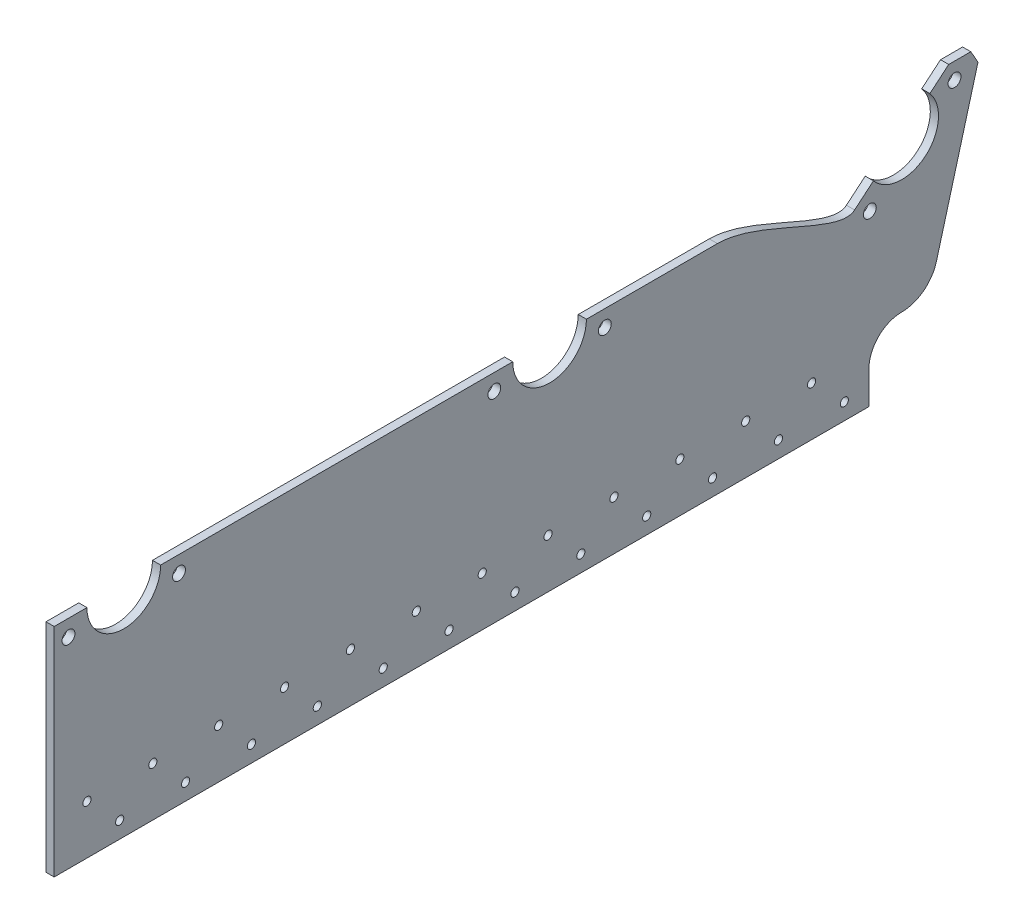
SolidWorks part; units mm, degrees
material "6061 Alloy"
ref_plane "Front Plane" through (0, 0, 0) normal (0, 0, 1) x (1, 0, 0)
ref_plane "Top Plane" through (0, 0, 0) normal (0, 1, 0) x (1, 0, 0)
ref_plane "Right Plane" through (0, 0, 0) normal (1, 0, 0) x (0, 0, -1)
sketch "Sketch1" plane through (0, 0, 0) normal (1, 0, 0) x (0, 0, -1)
  line L0 (-12.7, -12.7) -> (-328.6125, -12.7)
  line L1 (-328.6125, -12.7) -> (-328.6125, 71.4375)
  line L2 (-328.6125, 71.4375) -> (-315.9125, 71.4375)
  line L3 (-287.3375, 71.4375) -> (-150.8125, 71.4375)
  line L5 (10.9449, 80.6213) -> (18.2432, 86.7453)
  line L7 (-328.6125, 12.7) -> (13.4735, 12.7) construction
  line L8 (-12.7, -12.7) -> (-12.7, 0)
  line L9 (0, 12.4079) -> (0, 12.7) construction
  line L10 (13.4735, 22.9788) -> (30.9432, 86.7453)
  line L12 (-10.9449, 62.2537) -> (10.9449, 80.6213) construction
  line L13 (18.2432, 86.7453) -> (30.9432, 86.7453)
  line L14 (-122.2375, 71.4375) -> (-71.4375, 71.4375)
  line L15 (-10.9449, 62.2537) -> (-18.2432, 56.1297)
  line L16 (-328.6125, 15.875) -> (13.4735, 15.875) construction
  line L18 (0, 71.4375) -> (-136.525, 71.4375) construction
  arc A3 (0, 12.7) -> (13.4735, 22.9788) centre (0, 26.67) ccw
  arc A4 (0, 12.7) -> (-12.7, 0) centre (0, 0) ccw
  circle A5 centre (0, 0) radius 12.4079 construction
  arc A6 (-315.9125, 71.4375) -> (-287.3375, 71.4375) centre (-301.625, 71.4375) ccw
  arc A7 (-150.8125, 71.4375) -> (-122.2375, 71.4375) centre (-136.525, 71.4375) ccw
  arc A8 (-10.9449, 62.2537) -> (10.9449, 80.6213) centre (0, 71.4375) ccw
  spline S0 degree 3 poles (-18.2432, 56.1297) (-24.729, 50.6874) (-54.5042, 71.4375) (-71.4375, 71.4375) knots 0 0 0 0 1 1 1 1
  point P4 (-170.6562, -12.7)
  dimension "D1" = 25.4
  dimension "D3" = 12.7
  dimension "D5" = 28.575
  dimension "D6" = 41.275
  dimension "D7" = 13.97
  dimension "D8" = 12.7
  dimension "D10" = 24.8158
  dimension "D13" = 9.5273
  dimension "D14" = 140
  dimension "D15" = 50.8
  dimension "D16" = 50.8
  dimension "D17" = 25.4
  dimension "D2" = 0
  dimension "D4" = 12.7
  dimension "D9" = 12.7
  dimension "D11" = 301.625
  dimension "D12" = 301.625
  dimension "D18" = 3.175
extrude "Boss-Extrude1" add sketch "Sketch1" along normal blind 3.175
hole_wizard "#10 Clearance Hole1" positions "Sketch2" profile "Sketch3" hole size "#10" standard "ANSI Inch" end condition through all
sketch "Sketch2" plane through (3.175, 0, 0) normal (1, 0, 0) x (0, 0, -1)
  line L0 (-323.0562, 65.0875) -> (-280.1937, 65.0875) construction
  line L2 (-157.9562, 65.0875) -> (-115.0938, 65.0875) construction
  line L4 (-12.3356, 52.7974) -> (20.499, 80.3489) construction
  line L6 (-315.9125, 71.4375) -> (-328.6125, 71.4375) construction
  line L7 (-301.625, 65.0875) -> (-301.625, 71.4375) construction
  line L9 (-136.525, 71.4375) -> (-136.525, 65.0875) construction
  line L11 (0, 71.4375) -> (4.0817, 66.5731) construction
  line L14 (18.2432, 86.7453) -> (10.9449, 80.6213) construction
  line L15 (18.2432, 86.7453) -> (10.9449, 80.6213) construction
  point P0 (-323.0562, 65.0875)
  point P2 (-280.1937, 65.0875)
  point P4 (-157.9562, 65.0875)
  point P6 (-115.0938, 65.0875)
  point P8 (-12.3356, 52.7974)
  point P10 (20.499, 80.3489)
  dimension "D1" = 42.8625
  dimension "D2" = 6.35
  dimension "D3" = 6.35
sketch "Sketch3" plane through (3.175, 65.0875, 323.0562) normal (0, 1, 0) x (0, 0, -1)
  line L0 (0, 0) -> (0, 3.175)
  line L1 (0, 3.175) -> (2.4892, 3.175)
  line L2 (2.4892, 3.175) -> (2.4892, 0)
  line L5 (2.4892, 0) -> (0, 0)
  line L11 (0, -6.35) -> (0, 107.95) construction
  dimension "Thru Hole Dia." = 4.9784
  dimension "Thru Hole Depth" = 3.175
chamfer "Chamfer1" distance 5.08 angle 45 1 edges at (1.5875, 86.7453, -30.9432) first distance on face at (1.5875, 54.862, -22.2083)
sketch "Sketch4" plane through (3.175, 0, 0) normal (1, 0, 0) x (0, 0, -1)
  circle A0 centre (-315.9125, 6.35) radius 1.5875 construction
  circle A1 centre (-303.2125, -6.35) radius 1.5875 construction
  circle A2 centre (-290.3682, 6.35) radius 1.5875 construction
  circle A3 centre (-277.6682, -6.35) radius 1.5875 construction
  circle A4 centre (-264.8239, 6.35) radius 1.5875 construction
  circle A5 centre (-252.1239, -6.35) radius 1.5875 construction
  circle A6 centre (-239.2795, 6.35) radius 1.5875 construction
  circle A7 centre (-226.5795, -6.35) radius 1.5875 construction
  circle A8 centre (-213.7352, 6.35) radius 1.5875 construction
  circle A9 centre (-201.0352, -6.35) radius 1.5875 construction
  circle A10 centre (-188.1909, 6.35) radius 1.5875 construction
  circle A11 centre (-175.4909, -6.35) radius 1.5875 construction
  circle A12 centre (-162.6466, 6.35) radius 1.5875 construction
  circle A13 centre (-149.9466, -6.35) radius 1.5875 construction
  circle A14 centre (-137.1023, 6.35) radius 1.5875 construction
  circle A15 centre (-124.4023, -6.35) radius 1.5875 construction
  circle A16 centre (-111.558, 6.35) radius 1.5875 construction
  circle A17 centre (-98.858, -6.35) radius 1.5875 construction
  circle A18 centre (-86.0136, 6.35) radius 1.5875 construction
  circle A19 centre (-73.3136, -6.35) radius 1.5875 construction
  circle A20 centre (-60.4693, 6.35) radius 1.5875 construction
  circle A21 centre (-47.7693, -6.35) radius 1.5875 construction
  circle A22 centre (-34.925, 6.35) radius 1.5875 construction
  circle A23 centre (-22.225, -6.35) radius 1.5875 construction
  circle A24 centre (-315.9125, 6.35) radius 1.5875
  circle A25 centre (-303.2125, -6.35) radius 1.5875
  circle A26 centre (-290.3682, 6.35) radius 1.5875
  circle A27 centre (-277.6682, -6.35) radius 1.5875
  circle A28 centre (-264.8239, 6.35) radius 1.5875
  circle A29 centre (-252.1239, -6.35) radius 1.5875
  circle A30 centre (-239.2795, 6.35) radius 1.5875
  circle A31 centre (-226.5795, -6.35) radius 1.5875
  circle A32 centre (-213.7352, 6.35) radius 1.5875
  circle A33 centre (-201.0352, -6.35) radius 1.5875
  circle A34 centre (-188.1909, 6.35) radius 1.5875
  circle A35 centre (-175.4909, -6.35) radius 1.5875
  circle A36 centre (-162.6466, 6.35) radius 1.5875
  circle A37 centre (-149.9466, -6.35) radius 1.5875
  circle A38 centre (-137.1023, 6.35) radius 1.5875
  circle A39 centre (-124.4023, -6.35) radius 1.5875
  circle A40 centre (-111.558, 6.35) radius 1.5875
  circle A41 centre (-98.858, -6.35) radius 1.5875
  circle A42 centre (-86.0136, 6.35) radius 1.5875
  circle A43 centre (-73.3136, -6.35) radius 1.5875
  circle A44 centre (-60.4693, 6.35) radius 1.5875
  circle A45 centre (-47.7693, -6.35) radius 1.5875
  circle A46 centre (-34.925, 6.35) radius 1.5875
  circle A47 centre (-22.225, -6.35) radius 1.5875
extrude "Cut-Extrude1" cut sketch "Sketch4" against normal through all
